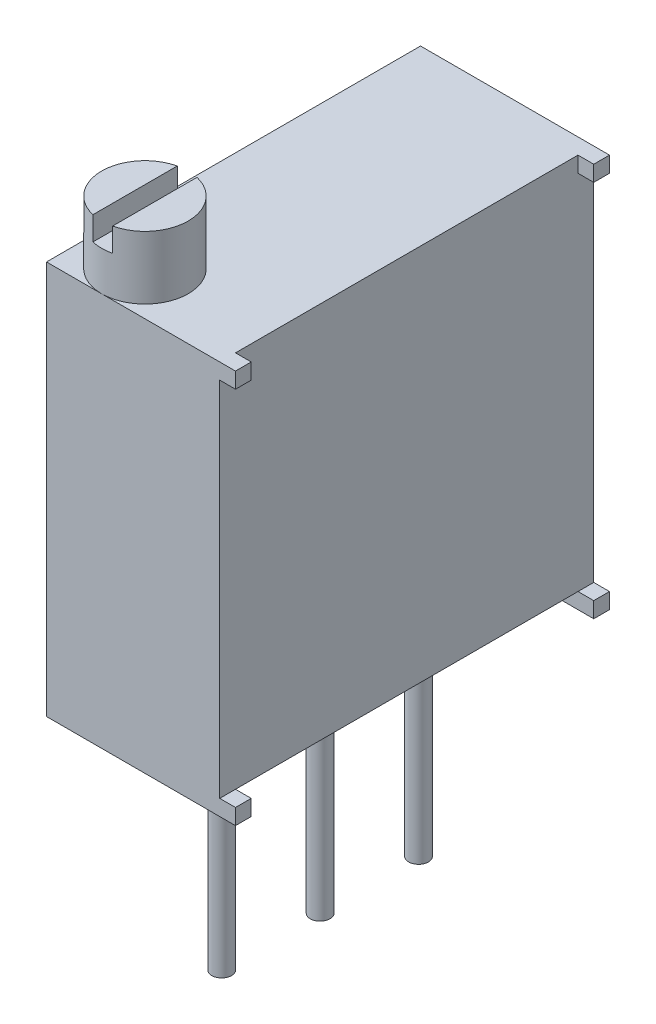
SolidWorks part; units mm, degrees
ref_plane "前视基准面" through (0, 0, 0) normal (0, 0, 1) x (1, 0, 0)
ref_plane "上视基准面" through (0, 0, 0) normal (0, 1, 0) x (1, 0, 0)
ref_plane "右视基准面" through (0, 0, 0) normal (1, 0, 0) x (0, 0, -1)
other "Configuration Table"
sketch "草图1" plane through (0, 0, 0) normal (1, 0, 0) x (0, 0, -1)
  line L1 (-4.75, -4.8) -> (4.75, -4.8)
  line L2 (-4.75, -4.8) -> (-4.75, 4.8)
  line L3 (-4.75, 4.8) -> (4.75, 4.8)
  line L4 (4.75, -4.8) -> (4.75, 4.8)
  line L5 (-4.75, -4.8) -> (4.75, 4.8) construction
  line L6 (-4.75, 4.8) -> (4.75, -4.8) construction
  line L7 (4.75, -4.8) -> (4.35, -4.8)
  line L8 (4.75, -4.8) -> (4.75, -5.2)
  line L9 (4.75, -5.2) -> (4.35, -5.2)
  line L10 (4.35, -4.8) -> (4.35, -5.2)
  line L11 (-4.75, -4.8) -> (-4.35, -4.8)
  line L12 (-4.75, -4.8) -> (-4.75, -5.2)
  line L13 (-4.75, -5.2) -> (-4.35, -5.2)
  line L14 (-4.35, -4.8) -> (-4.35, -5.2)
  line L15 (4.75, 4.8) -> (4.35, 4.8)
  line L16 (4.75, 4.8) -> (4.75, 4.4)
  line L17 (4.75, 4.4) -> (4.35, 4.4)
  line L18 (4.35, 4.8) -> (4.35, 4.4)
  line L19 (-4.75, 4.8) -> (-4.35, 4.8)
  line L20 (-4.75, 4.8) -> (-4.75, 4.4)
  line L21 (-4.75, 4.4) -> (-4.35, 4.4)
  line L22 (-4.35, 4.8) -> (-4.35, 4.4)
  point P0 (0, 0)
  dimension "D1" = 9.6
  dimension "D2" = 9.5
  dimension "D3" = 0.4
extrude "凸台-拉伸1" add sketch "草图1" along normal blind 4.4 contours L3 L22 L21 L2 L1 L4 L17 L18 region at (0, -0.0162, 0)
extrude "凸台-拉伸2" add sketch "草图1<4>" along normal blind 4.8 contours L3 L18 L17 L4 | L1 L10 L9 L8 | L19 L22 L21 L20 | L11 L14 L13 L12 region at (0, -5, -4.55) region at (0, 4.6, -4.55)
sketch "草图1<4>" plane through (0, 0, 0) normal (1, 0, 0) x (0, 0, -1) same geometry as "草图1"
sketch "草图2" plane through (0, 4.8, 0) normal (0, 1, 0) x (1, 0, 0)
  line L0 (4.8, -4.75) -> (0, -4.75) construction
  line L2 (0, -4.75) -> (0, 4.75) construction
  line L4 (1.15, -4.75) -> (1.65, -4.75)
  line L5 (1.15, -4.75) -> (1.15, -2.55)
  line L6 (1.15, -2.55) -> (1.65, -2.55)
  line L7 (1.65, -4.75) -> (1.65, -2.55)
  circle A0 centre (1.4, -3.65) radius 1.1
  dimension "D1" = 2.2
  dimension "D2" = 1.1
  dimension "D3" = 1.4
  dimension "D4" = 0.5
  dimension "D5" = 0.25
extrude "凸台-拉伸3" add sketch "草图2" along normal blind 1.6 contours A0
extrude "切除-拉伸2" cut sketch "草图2<5>" against normal blind 0.6 from surface contours L5 L6 L7 L4 starting at face at (1.4, 6.4, 4.75)
sketch "草图2<5>" plane through (0, 4.8, 0) normal (0, 1, 0) x (1, 0, 0) same geometry as "草图2"
sketch "草图3" plane through (0, -4.8, 0) normal (0, -1, 0) x (1, 0, 0)
  line L0 (0, 0) -> (4.4, 0) construction
  line L1 (0, 4.35) -> (0, -4.35) construction
  line L2 (4.4, 4.35) -> (4.4, -4.35) construction
  line L3 (2.2, 4.35) -> (2.2, -4.35) construction
  line L5 (4.4, 4.35) -> (0, 4.35) construction
  line L6 (4.4, -4.35) -> (0, -4.35) construction
  line L7 (2.2, 2.5) -> (2.2, -2.5) construction
  circle A0 centre (2.2, 0) radius 0.25
  circle A1 centre (2.2, 2.5) radius 0.25
  circle A2 centre (2.2, -2.5) radius 0.25
  dimension "D2" = 0.5
  dimension "D1" = 5
extrude "凸台-拉伸4" add sketch "草图3" along normal blind 6
